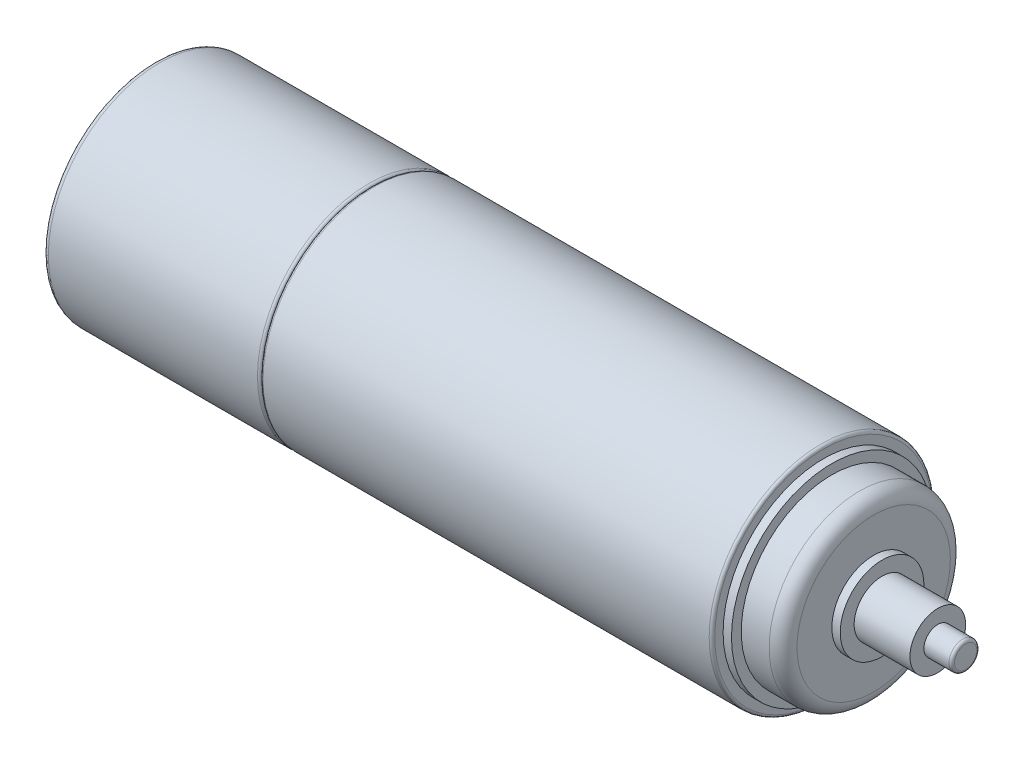
SolidWorks part; units mm, degrees
ref_plane "Front Plane" through (0, 0, 0) normal (0, 0, 1) x (1, 0, 0)
ref_plane "Top Plane" through (0, 0, 0) normal (0, 1, 0) x (1, 0, 0)
ref_plane "Right Plane" through (0, 0, 0) normal (1, 0, 0) x (0, 0, -1)
sketch "Sketch1" plane through (0, 0, 0) normal (1, 0, 0) x (0, 0, -1)
  circle A0 centre (-12.114, -15.3494) radius 4
  dimension "D1" = 8
extrude "Boss-Extrude1" add sketch "Sketch1" along normal blind 16.2
sketch "Sketch2" plane through (16.2, 0, 0) normal (1, 0, 0) x (0, 0, -1)
  circle A0 centre (-12.114, -15.3494) radius 3.6
  dimension "D1" = 7.2
extrude "Boss-Extrude2" add sketch "Sketch2" along normal blind 0.3
sketch "Sketch3" plane through (16.5, 0, 0) normal (1, 0, 0) x (0, 0, -1)
  circle A0 centre (-12.114, -15.3494) radius 3.25
  dimension "D1" = 6.5
extrude "Boss-Extrude3" add sketch "Sketch3" along normal blind 1.5
fillet "Fillet1" radius 0.5 1 edges at (18, -15.3494, 8.864)
sketch "Sketch4" plane through (18, 0, 0) normal (1, 0, 0) x (0, 0, -1)
  circle A0 centre (-12.114, -15.3494) radius 1.5
  dimension "D1" = 3
extrude "Boss-Extrude4" add sketch "Sketch4" along normal blind 0.3
sketch "Sketch5" plane through (18.3, 0, 0) normal (1, 0, 0) x (0, 0, -1)
  circle A0 centre (-12.114, -15.3494) radius 1
  dimension "D1" = 2
extrude "Boss-Extrude5" add sketch "Sketch5" along normal blind 2
sketch "Sketch6" plane through (20.3, 0, 0) normal (1, 0, 0) x (0, 0, -1)
  circle A0 centre (-12.114, -15.3494) radius 0.5
  dimension "D1" = 1
extrude "Boss-Extrude6" add sketch "Sketch6" along normal blind 1
fillet "Fillet2" radius 0.1 1 edges at (0, -15.3494, 8.114)
fillet "Fillet3" radius 0.1 1 edges at (16.2, -15.3494, 8.114)
sketch "Sketch7" plane through (0, 0, 0) normal (-1, 0, 0) x (0, 0, 1)
  circle A0 centre (12.114, -15.3494) radius 4
extrude "Boss-Extrude7" add sketch "Sketch7" along normal blind 7.8
fillet "Fillet4" radius 0.2 1 edges at (-7.8, -15.3494, 16.114)
fillet "Fillet5" radius 0.1 1 edges at (0, -15.3494, 16.114)
fillet "Fillet6" radius 0.1 1 edges at (21.3, -15.3494, 11.614)
